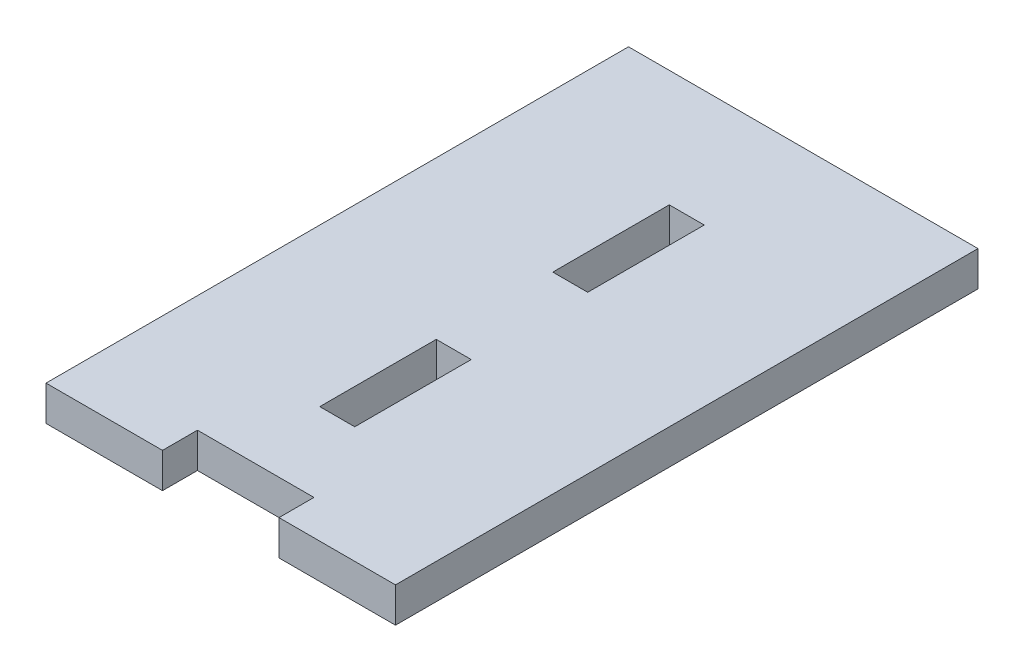
SolidWorks part; units mm, degrees
ref_plane "Alzado" through (0, 0, 0) normal (0, 0, 1) x (1, 0, 0)
ref_plane "Planta" through (0, 0, 0) normal (0, 1, 0) x (1, 0, 0)
ref_plane "Vista lateral" through (0, 0, 0) normal (1, 0, 0) x (0, 0, -1)
sketch "Croquis1" plane through (0, 0, 0) normal (0, 1, 0) x (1, 0, 0)
  line L0 (25, 0) -> (35, 0)
  line L1 (15, 3) -> (15, 0)
  line L2 (5, 0) -> (5, 50)
  line L3 (35, 0) -> (35, 50)
  line L5 (18.5, 10) -> (21.5, 10)
  line L6 (21.5, 10) -> (21.5, 20)
  line L7 (21.5, 20) -> (18.5, 20)
  line L8 (35, 50) -> (5, 50)
  line L9 (15, 3) -> (25, 3)
  line L10 (21.5, 30) -> (18.5, 30)
  line L11 (21.5, 40) -> (21.5, 30)
  line L12 (18.5, 40) -> (21.5, 40)
  line L13 (25, 3) -> (25, 0)
  line L14 (18.5, 40) -> (18.5, 30)
  line L15 (18.5, 10) -> (18.5, 20)
  line L16 (15, 0) -> (5, 0)
  point P12 (20, 50)
  dimension "D1" = 3
  dimension "D3" = 50
  dimension "D5" = 10
extrude "Saliente-Extruir1" add sketch "Croquis1" along normal blind 3
